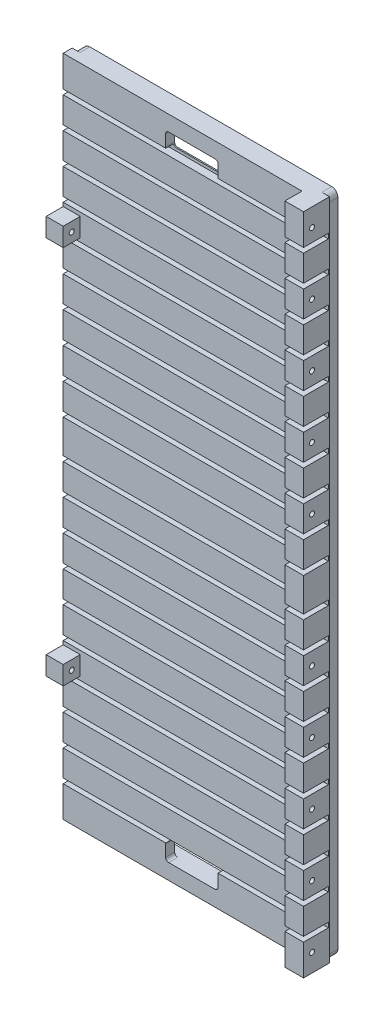
SolidWorks part; units mm, degrees
ref_plane "Front Plane" through (0, 0, 0) normal (0, 0, 1) x (1, 0, 0)
ref_plane "Top Plane" through (0, 0, 0) normal (0, 1, 0) x (1, 0, 0)
ref_plane "Right Plane" through (0, 0, 0) normal (1, 0, 0) x (0, 0, -1)
sketch "Sketch1" plane through (0, 0, 0) normal (0, 0, 1) x (1, 0, 0)
  line L1 (-41.5, -107) -> (41.5, -107)
  line L2 (-41.5, -107) -> (-41.5, 107)
  line L3 (-41.5, 107) -> (41.5, 107)
  line L4 (41.5, -107) -> (41.5, 107)
  line L5 (-41.5, -107) -> (41.5, 107) construction
  line L6 (-41.5, 107) -> (41.5, -107) construction
  point P0 (0, 0)
  dimension "D1" = 83
  dimension "D2" = 214
extrude "Boss-Extrude1" add sketch "Sketch1" along normal blind 8.4
sketch "Sketch2" plane through (0, 107, 0) normal (0, 1, 0) x (1, 0, 0)
  line L0 (41.5, -8.4) -> (41.5, 0) construction
  line L1 (-41.5, -8.4) -> (35.5, -8.4)
  line L2 (-41.5, -8.4) -> (-41.5, -2.9)
  line L3 (-41.5, -2.9) -> (35.5, -2.9)
  line L4 (35.5, -8.4) -> (35.5, -2.9)
  dimension "D1" = 5.5
  dimension "D2" = 6
extrude "Cut-Extrude1" cut sketch "Sketch2" against normal through all
sketch "Sketch3" plane through (41.5, 0, 0) normal (1, 0, 0) x (0, 0, -1)
  line L0 (-8.4, -107) -> (-8.4, 107) construction
  line L1 (-8.4, 97) -> (-0.4, 97)
  line L2 (-8.4, 97) -> (-8.4, 95.4)
  line L3 (-8.4, 95.4) -> (-0.4, 95.4)
  line L4 (-0.4, 97) -> (-0.4, 95.4)
  line L5 (-8.4, 107) -> (0, 107) construction
  dimension "D1" = 1.6
  dimension "D2" = 8
  dimension "D3" = 10
extrude "Cut-Extrude2" cut sketch "Sketch3" against normal through all
pattern_linear "LPattern1" count 10 spacing 10 along (0, -1, 0) of "Cut-Extrude2"
mirror "Mirror1" about plane through (0, 0, 0) normal (0, 1, 0) of "LPattern1"
sketch "Sketch4" plane through (0, 0, 0) normal (0, 0, -1) x (-1, 0, 0)
  line L0 (-41.5, 107) -> (41.5, 107) construction
  line L1 (-39, 107) -> (39, 107)
  line L2 (-41, 105) -> (-41, -105)
  line L3 (-39, -107) -> (39, -107)
  line L4 (41, 105) -> (41, -105)
  line L5 (-33.5, -102) -> (33.5, -102)
  line L6 (-35.5, -100) -> (-35.5, 100)
  line L7 (-33.5, 102) -> (33.5, 102)
  line L8 (35.5, -100) -> (35.5, 100)
  line L9 (-35.5, -102) -> (35.5, 102) construction
  line L10 (-35.5, 102) -> (35.5, -102) construction
  line L11 (41.5, -107) -> (-41.5, -107) construction
  arc A0 (-41, -105) -> (-39, -107) centre (-39, -105) ccw
  arc A1 (39, -107) -> (41, -105) centre (39, -105) ccw
  arc A2 (39, 107) -> (41, 105) centre (39, 105) cw
  arc A3 (-39, 107) -> (-41, 105) centre (-39, 105) ccw
  arc A4 (33.5, -102) -> (35.5, -100) centre (33.5, -100) ccw
  arc A5 (-33.5, -102) -> (-35.5, -100) centre (-33.5, -100) cw
  arc A6 (-35.5, 100) -> (-33.5, 102) centre (-33.5, 100) cw
  arc A7 (33.5, 102) -> (35.5, 100) centre (33.5, 100) cw
  point P10 (41.5, -107)
  point P15 (-41.5, 107)
  point P16 (0, 0)
  dimension "D1" = 2
  dimension "D4" = 2
  dimension "D2" = 5
  dimension "D3" = 5.5
  dimension "D5" = 41
  dimension "D6" = 41
extrude "Boss-Extrude2" add sketch "Sketch4" along normal blind 3.18
sketch "Sketch5" plane through (0, 0, 2.9) normal (0, 0, 1) x (1, 0, 0)
  line L0 (-41.5, 57) -> (-41.5, 65.4) construction
  line L1 (-36, 58.2) -> (-41.5, 58.2)
  line L2 (-36, 58.2) -> (-36, 64.2)
  line L3 (-36, 64.2) -> (-41.5, 64.2)
  line L4 (-41.5, 58.2) -> (-41.5, 64.2)
  line L5 (-36, 58.2) -> (-41.5, 64.2) construction
  line L6 (-36, 64.2) -> (-41.5, 58.2) construction
  line L8 (35.5, 65.4) -> (-41.5, 65.4) construction
  point P0 (-38.75, 61.2)
  dimension "D1" = 6
  dimension "D2" = 5.5
  dimension "D3" = 4.2
extrude "Boss-Extrude3" add sketch "Sketch5" along normal blind 5.5
mirror "Mirror2" about plane through (0, 0, 0) normal (0, 1, 0) of "Boss-Extrude3"
sketch "Sketch6" plane through (0, 0, 0) normal (0, 0, -1) x (-1, 0, 0)
  line L0 (33.5, 102) -> (-33.5, 102) construction
  line L1 (-7.475, 96.3) -> (7.475, 96.3)
  line L2 (-8.475, 97.3) -> (-8.475, 101)
  line L3 (-7.475, 102) -> (7.475, 102)
  line L4 (8.475, 97.3) -> (8.475, 101)
  line L5 (-8.475, 96.3) -> (8.475, 102) construction
  line L6 (-8.475, 102) -> (8.475, 96.3) construction
  arc A0 (-8.475, 101) -> (-7.475, 102) centre (-7.475, 101) cw
  arc A1 (7.475, 102) -> (8.475, 101) centre (7.475, 101) cw
  arc A2 (7.475, 96.3) -> (8.475, 97.3) centre (7.475, 97.3) ccw
  arc A3 (-7.475, 96.3) -> (-8.475, 97.3) centre (-7.475, 97.3) cw
  point P0 (0, 99.15)
  dimension "D3" = 1
  dimension "D1" = 5.7
  dimension "D2" = 16.95
extrude "Cut-Extrude3" cut sketch "Sketch6" against normal through all
mirror "Mirror3" about plane through (0, 0, 0) normal (0, 1, 0) of "Cut-Extrude3"
hole_wizard "M2x0.4 Tapped Hole1" positions "Sketch8" profile "Sketch7" tap size "M2x0.4" standard "ANSI Metric" end condition through all
sketch "Sketch8" plane through (41.5, 0, 0) normal (1, 0, 0) x (0, 0, -1)
  line L0 (-8.4, 97) -> (-8.4, 107) construction
  line L1 (-8.4, 107) -> (0, 107) construction
  line L2 (0, 0) -> (-25.7972, 0) construction
  line L3 (0, -107) -> (0, 107) construction
  point P0 (-5.65, 101.2)
  point P16 (-5.65, 81.2)
  point P17 (-5.65, 61.2)
  point P18 (-5.65, 41.2)
  point P19 (-5.65, 21.2)
  point P34 (-5.65, -101.2)
  point P35 (-5.65, -81.2)
  point P36 (-5.65, -61.2)
  point P37 (-5.65, -41.2)
  point P38 (-5.65, -21.2)
  dimension "D1" = 2.75
  dimension "D2" = 5.8
  dimension "D3" = 5
sketch "Sketch7" plane through (41.5, 101.2, 5.65) normal (0, 1, 0) x (0, 0, -1)
  line L0 (0, 0) -> (0, 83)
  line L1 (0, 83) -> (0.8, 83)
  line L2 (0.8, 83) -> (0.8, 0)
  line L5 (0.8, 0) -> (0, 0)
  line L11 (0, -6.35) -> (0, 107.95) construction
  dimension "Thread Major Dia." = 1.6
  dimension "Thru Tap Drill Depth" = 83
hole_wizard "M2x0.4 Tapped Hole2" positions "Sketch10" profile "Sketch11" tap size "M2x0.4" standard "ANSI Metric"
sketch "Sketch10" plane through (0, 0, -3.18) normal (0, 0, -1) x (-1, 0, 0)
  line L0 (39, 107) -> (-39, 107) construction
  line L1 (-41, 105) -> (-41, -105) construction
  line L3 (-35.5, 0) -> (35.5, 0) construction
  line L4 (-35.5, 100) -> (-35.5, -100) construction
  line L5 (35.5, -100) -> (35.5, 100) construction
  point P0 (-37.5, 101.2)
  point P15 (37.5, 101.2)
  point P16 (37.5, 81.2)
  point P17 (37.5, 61.2)
  point P18 (37.5, 41.2)
  point P19 (37.5, 21.2)
  point P20 (-37.5, 81.2)
  point P21 (-37.5, 61.2)
  point P22 (-37.5, 41.2)
  point P23 (-37.5, 21.2)
  point P32 (37.5, -101.2)
  point P33 (-37.5, -21.2)
  point P34 (-37.5, -41.2)
  point P35 (-37.5, -61.2)
  point P36 (-37.5, -81.2)
  point P37 (37.5, -21.2)
  point P38 (37.5, -41.2)
  point P39 (37.5, -61.2)
  point P40 (37.5, -81.2)
  point P41 (-37.5, -101.2)
  dimension "D1" = 5.8
  dimension "D2" = 3.5
  dimension "D5" = 2
  dimension "D3" = 5
sketch "Sketch11" plane through (37.5, 101.2, -3.18) normal (1, 0, 0) x (0, 1, 0)
  line L0 (0, 0) -> (0, 4.4807)
  line L1 (0, 4.4807) -> (0.8, 4)
  line L2 (0.8, 4) -> (0.8, 0)
  line L5 (0.8, 0) -> (0, 0)
  line L10 (0, 4.4807) -> (-0.8, 4) construction
  line L11 (0, -6.35) -> (0, 107.95) construction
  dimension "Tap Drill Dia." = 1.6
  dimension "Tap Drill Depth" = 4
  dimension "Drill Angle" = 118
